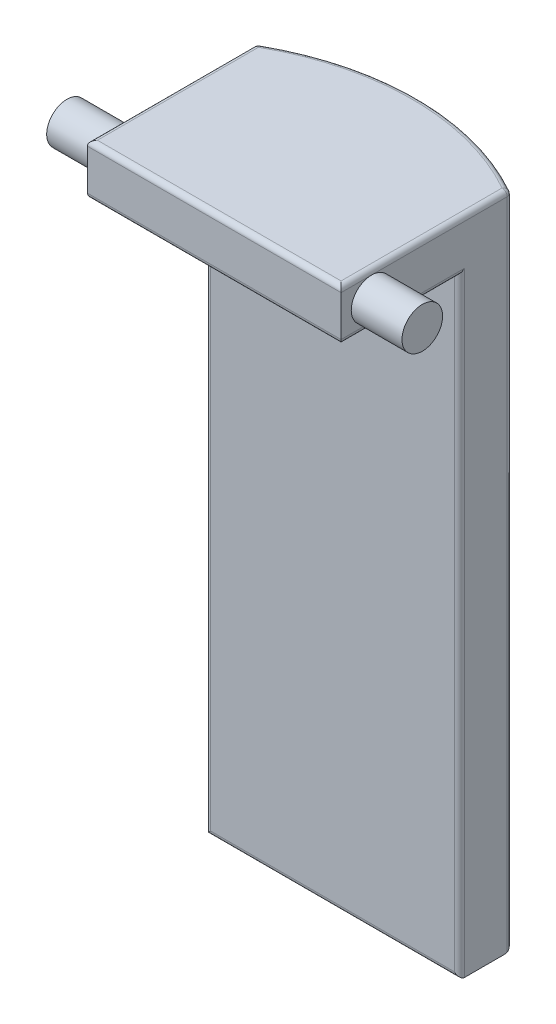
SolidWorks part; units mm, degrees
material "ABS"
ref_plane "Front Plane" through (0, 0, 0) normal (0, 0, 1) x (1, 0, 0)
ref_plane "Top Plane" through (0, 0, 0) normal (0, 1, 0) x (1, 0, 0)
ref_plane "Right Plane" through (0, 0, 0) normal (1, 0, 0) x (0, 0, -1)
sketch "Sketch1" plane through (0, 0, 0) normal (0, 1, 0) x (1, 0, 0)
  circle A0 centre (0, 0) radius 25
  dimension "D1" = 50
extrude "Boss-Extrude1" add sketch "Sketch1" against normal blind 69
sketch "Sketch2" plane through (0, 0, 0) normal (0, 1, 0) x (1, 0, 0)
  line L0 (0, 33.9524) -> (0, -35.65) construction
  line L1 (-12.5, 21.6506) -> (-12.5, -21.6506)
  line L2 (12.5, 21.6506) -> (12.5, -21.6506)
  line L3 (-26.3131, -47.722) -> (-26.3131, -48.0992)
  circle A0 centre (0, 0) radius 25 construction
  arc A3 (-12.5, 21.6506) -> (-12.5, -21.6506) centre (0, 0) ccw
  arc A4 (12.5, -21.6506) -> (12.5, 21.6506) centre (0, 0) ccw
  circle M6 centre (0, 0) radius 25
  dimension "D1" = 12.5
extrude "Cut-Extrude3" cut sketch "Sketch2" against normal blind 69 contours L1 M6 | L2 M6 region at (-17.6255, 0, 0) region at (17.6255, 0, 0)
sketch "Sketch8" plane through (12.5, 0, 0) normal (1, 0, 0) x (0, 0, -1)
  line L1 (0, 13.4389) -> (-47.6135, 13.4389)
  line L2 (0, 13.4389) -> (0, -82.6558)
  line L3 (0, -82.6558) -> (-47.6135, -82.6558)
  line L4 (-47.6135, 13.4389) -> (-47.6135, -82.6558)
  line L5 (0, 13.4389) -> (-47.6135, -82.6558) construction
  line L6 (0, -82.6558) -> (-47.6135, 13.4389) construction
  point P4 (-23.8068, -34.6085)
extrude "Cut-Extrude6" cut sketch "Sketch8" against normal blind 69
sketch "Sketch9" plane through (12.5, 0, 0) normal (1, 0, 0) x (0, 0, -1)
  line L0 (0, -69) -> (0, 0) construction
  line L1 (0, -5) -> (16.6506, -5)
  line L2 (0, -5) -> (0, -69)
  line L3 (0, -69) -> (16.6506, -69)
  line L4 (16.6506, -5) -> (16.6506, -69)
  line L5 (0, -5) -> (16.6506, -69) construction
  line L6 (0, -69) -> (16.6506, -5) construction
  line L7 (21.6506, -69) -> (0, -69) construction
  line L8 (21.6506, 0) -> (0, 0) construction
  line L9 (21.6506, -69) -> (21.6506, 0) construction
  point P4 (8.3253, -37)
  dimension "D1" = 5
  dimension "D2" = 5
extrude "Cut-Extrude7" cut sketch "Sketch9" against normal blind 69
sketch "Sketch10" plane through (12.5, 0, 0) normal (1, 0, 0) x (0, 0, -1)
  line L1 (0, 0) -> (5, 0)
  line L2 (0, 0) -> (0, -9.2319)
  line L3 (0, -9.2319) -> (5, -9.2319)
  line L4 (5, 0) -> (5, -9.2319)
  line L5 (0, 0) -> (5, -9.2319) construction
  line L6 (0, -9.2319) -> (5, 0) construction
  point P4 (2.5, -4.6159)
  dimension "D1" = 5
extrude "Cut-Extrude8" cut sketch "Sketch10" against normal blind 69
sketch "Sketch11" plane through (12.5, 0, 0) normal (1, 0, 0) x (0, 0, -1)
  line L0 (5, -5) -> (5, 0) construction
  circle A0 centre (8, -2.5) radius 2
  dimension "D1" = 4
  dimension "D2" = 3
extrude "Boss-Extrude2" add sketch "Sketch11" along normal blind 5 and the other way blind 30
sketch "Sketch12" plane through (12.5, 0, 0) normal (1, 0, 0) x (0, 0, -1)
  line L1 (16.6506, -69) -> (38.5748, -69)
  line L2 (16.6506, -69) -> (16.6506, -65)
  line L3 (16.6506, -65) -> (38.5748, -65)
  line L4 (38.5748, -69) -> (38.5748, -65)
  line L5 (16.6506, -69) -> (38.5748, -65) construction
  line L6 (16.6506, -65) -> (38.5748, -69) construction
  point P4 (27.6127, -67)
  dimension "D1" = 4
extrude "Cut-Extrude9" cut sketch "Sketch12" against normal through all
fillet "Fillet1" radius 0.5 13 edges at (-12.5, 0, -13.3253) (0, 0, -25) (12.5, 0, -13.3253) (0, 0, -5) (0, -65, -16.6506) (0, -65, -25) (0, -5, -5) (12.5, -5, -10.8253) (-12.5, -5, -10.8253) (-12.5, -35, -16.6506) (-12.5, -32.5, -21.6506) (12.5, -35, -16.6506) (12.5, -32.5, -21.6506)
